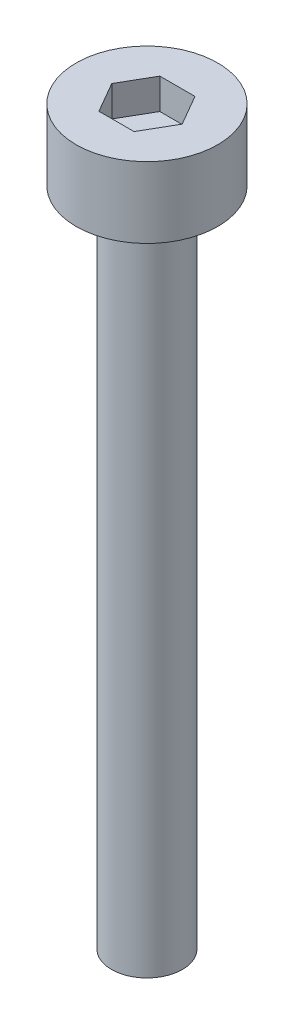
SolidWorks part; units mm, degrees
ref_plane "Front Plane" through (0, 0, 0) normal (0, 0, 1) x (1, 0, 0)
ref_plane "Top Plane" through (0, 0, 0) normal (0, 1, 0) x (1, 0, 0)
ref_plane "Right Plane" through (0, 0, 0) normal (1, 0, 0) x (0, 0, -1)
sketch "Sketch1" plane through (0, 0, 0) normal (0, 1, 0) x (1, 0, 0)
  circle A0 centre (0, 0) radius 1.5
  dimension "D1" = 3
extrude "ScrewShaft" add sketch "Sketch1" along normal blind 28
sketch "Sketch2" plane through (0, 28, 0) normal (0, 1, 0) x (1, 0, 0)
  circle A0 centre (0, 0) radius 3
  dimension "D1" = 6
extrude "Boss-Extrude2" add sketch "Sketch2" along normal blind 3
sketch "Sketch3" plane through (0, 31, 0) normal (0, 1, 0) x (1, 0, 0)
  line L0 (0, 0) -> (0, 1.29) construction
  line L1 (1.4896, 0) -> (0.7448, 1.29)
  line L2 (0.7448, 1.29) -> (-0.7448, 1.29)
  line L3 (-0.7448, 1.29) -> (-1.4896, 0)
  line L4 (-1.4896, 0) -> (-0.7448, -1.29)
  line L5 (-0.7448, -1.29) -> (0.7448, -1.29)
  line L6 (0.7448, -1.29) -> (1.4896, 0)
  circle A0 centre (0, 0) radius 1.29 construction
  dimension "D1" = 2.58
extrude "Cut-Extrude1" cut sketch "Sketch3" against normal blind 1.3
equation "\"X-ROD-SPACING\"=45"
equation "\"Y-ROD-SPACING\"=75"
equation "\"Z-ROD-SPACING\"=17.5"
equation "\"Y-BED-OFFSET\"=2"
equation "\"Y-BED-ROD-INSET\"=3.5"
equation "\"T-SLOT-NUT-FILLET-RADIUS\"=0.5"
equation "\"T-SLOT-SCREW-SHAFT-RADIUS\"=1.55"
equation "\"T-SLOT-SCREW-SHAFT-CUTOUT-LENGTH\"=11.0"
equation "\"T-SLOT-NUT-DEPTH\"=3.5"
equation "\"T-SLOT-NUT-WIDTH\"=2.85"
equation "\"T-SLOT-NUT-END-DISTANCE\"=8"
equation "\"ACRYLIC-THICKNESS\"=10"
equation "\"ACRYLIC-THICKNESS2\"=4.5"
equation "\"ACRYLIC-TAB-CUTOUT-SIZE\"=\"ACRYLIC-THICKNESS\"+\"ACRYLIC-TAB-TOLERANCE\"*2"
equation "\"ACRYLIC-TAB-WIDTH\"=\"ACRYLIC-THICKNESS\""
equation "\"ACRYLIC-M3-HOLE\"=2.9"
equation "\"SMOOTHROD-CAP-SCREW-DISTANCE\"=20"
equation "\"FRAME-WIDTH-INNER\"=370"
equation "\"NEMA17-HOLE-SPACING\"=31"
equation "\"NEMA17-CENTRAL-CUTOUT\"=22.5"
equation "\"Z-BRACKET-REACH\"=55"
equation "\"TOP-BRACKET-SPACING\"=40"
equation "\"SMOOTHROD-X-LENGTH\"=350"
equation "\"SMOOTHROD-Y-LENGTH\"=350"
equation "\"SMOOTHROD-Z-LENGTH\"=350"
equation "\"SMOOTHROD-TIGHTENING-HEADROOM\"=.25"
equation "\"LEADSCREW-Z-LENGTH\"=300"
equation "\"SCREW-LENGTH-FRAME\"=\"ACRYLIC-THICKNESS\" + 10"
equation "\"SCREW-HEAD-RADIUS\"=6"
equation "\"PRINTED-X-SMOOTHROD-DIAMETER\"=8.4"
equation "\"PRINTED-X-SMOOTHROD-CUTOUT\"=10"
equation "\"PRINTED-X-BASE-HEIGHT\"=10"
equation "\"PRINTED-LM8UU-CUTOUT-SIZE\"=15.5"
equation "\"PRINTED-LM8UU-CUTOUT-LENGTH\"=24.5"
equation "\"PRINTED-X-IDLER-HEIGHT\"=16"
equation "\"PSU-MOUNTING-WIDTH\"=95"
equation "\"PSU-MOUNTING-HEIGHT\"=177"
equation "\"D1@ScrewShaft\"=\"SCREW-LENGTH-EXTRUDER\""
equation "\"D1@Sketch2\"=\"SCREW-HEAD-RADIUS\""
equation "\"Y-BED-SCREW-SPACING\"=209"
equation "\"Y-BED-SCREW-CUTOUT-SLOT-HEIGHT\"=2"
equation "\"Z-ROD-INSET\"=16"
equation "\"SCREW-LENGTH-MOTOR\"=\"ACRYLIC-THICKNESS\" + 5"
equation "\"SCREW-LENGTH-EXTRUDER\"=28"
equation "\"Y-BELT-TO-ROD-DISTANCE\"=20"
equation "\"SPOOL-HOLDER-ROD-SPACING\"=150"
equation "\"ACRYLIC-X-CARRIAGE-WIDTH\"=55"
equation "\"ACRYLIC-X-CARRIAGE-HEIGHT\"=75"
equation "\"ACRYLIC-X-CARRIAGE-CENTER-TAB-SPACING\"=14"
